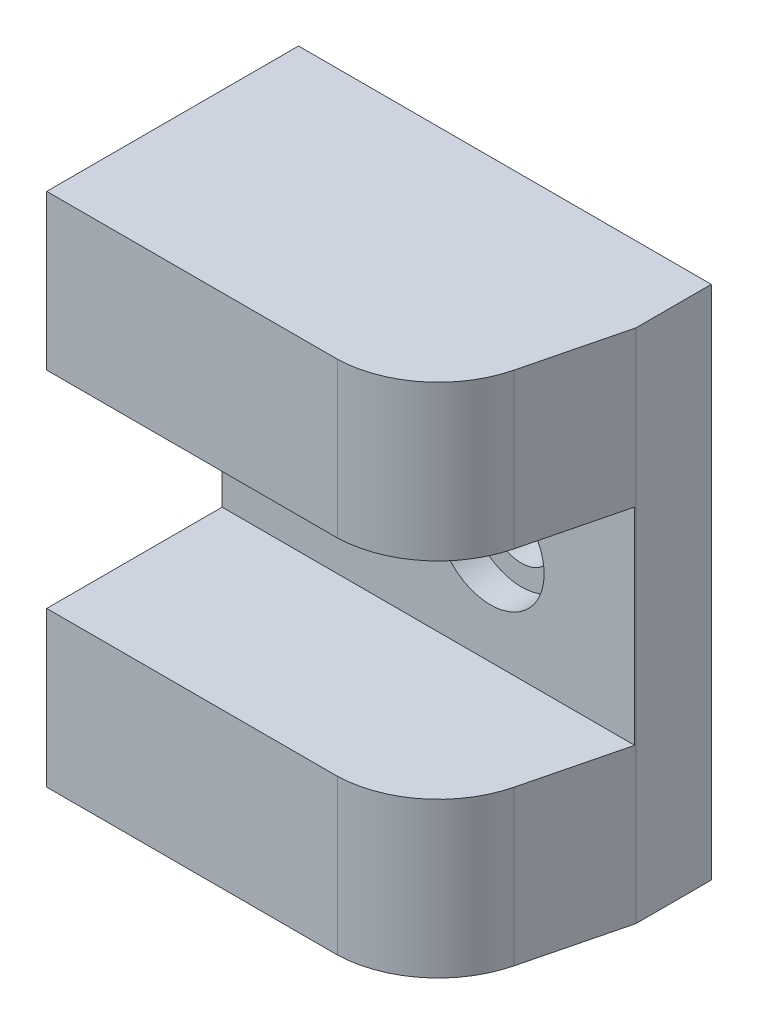
SolidWorks part; units mm, degrees
ref_plane "前视基准面" through (0, 0, 0) normal (0, 0, 1) x (1, 0, 0)
ref_plane "上视基准面" through (0, 0, 0) normal (0, 1, 0) x (1, 0, 0)
ref_plane "右视基准面" through (0, 0, 0) normal (1, 0, 0) x (0, 0, -1)
sketch "草图1" plane through (0, 0, 0) normal (0, 0, 1) x (1, 0, 0)
  line L0 (130, 105) -> (130, -105) construction
  line L1 (130, 80) -> (110, 80)
  line L2 (130, 80) -> (130, 105)
  line L4 (110, 80) -> (110, 105)
  line L5 (75, 105) -> (130, 105) construction
  line L6 (130, 105) -> (110, 105)
  dimension "D1" = 20
  dimension "D2" = 25
extrude "凸台-拉伸1" add sketch "草图1" along normal blind 12.2
sketch "草图2" plane through (0, 105, 0) normal (0, 1, 0) x (1, 0, 0)
  line L0 (130, -12.2) -> (130, 0) construction
  line L6 (128.82, -8.3843) -> (130, -3.6517)
  line L7 (128.9829, -8.558) -> (143.1288, 48.1782) construction
  line L8 (130, -3.6517) -> (130, -12.2)
  line L9 (128.9829, -8.558) -> (143.1288, 48.1782) construction
  line L10 (130, -12.2) -> (124.083, -12.2)
  line L11 (130, -12.2) -> (110, -12.2) construction
  arc A0 (123.9373, -12.5) -> (128.9829, -8.558) centre (123.9373, -7.3) ccw construction
  arc A1 (124.083, -12.2) -> (128.82, -8.3843) centre (123.9333, -7.1659) ccw
  arc A2 (123.9373, -12.5) -> (128.9829, -8.558) centre (123.9373, -7.3) ccw construction
  point P0 (123.9373, -7.1659)
  dimension "D1" = 5.917
  dimension "D2" = 0.4
extrude "切除-拉伸1" cut sketch "草图2" against normal blind 26.5
sketch "草图3" plane through (0, 0, 12.2) normal (0, 0, 1) x (1, 0, 0)
  line L0 (110, 92.5) -> (130, 92.5) construction
  line L1 (110, 105) -> (110, 80) construction
  line L4 (110, 97.5) -> (130, 97.5)
  line L5 (110, 97.5) -> (110, 87.5)
  line L6 (110, 87.5) -> (130, 87.5)
  line L7 (130, 97.5) -> (130, 87.5)
  line L8 (110, 97.5) -> (130, 87.5) construction
  line L9 (110, 87.5) -> (130, 97.5) construction
  point P6 (120, 92.5)
  dimension "D1" = 10
  dimension "D2" = 20
extrude "切除-拉伸2" cut sketch "草图3" against normal blind 8.5
sketch "草图4" plane through (0, 0, 3.7) normal (0, 0, 1) x (1, 0, 0)
  line L0 (110, 92.5) -> (129.988, 92.5) construction
  line L1 (110, 97.5) -> (110, 87.5) construction
  line L2 (129.988, 87.5) -> (129.988, 97.5) construction
  circle A0 centre (115, 92.5) radius 1.5
  circle A2 centre (123, 92.5) radius 1.5
  point P4 (0, 0)
  point P5 (129.988, 92.5)
  dimension "D1" = 3
  dimension "D2" = 8
  dimension "D3" = 5
hole_wizard "M3 六角头螺栓的柱形沉头孔1" positions "草图7" profile "草图8" counterbore size "M3" standard "GB" end condition through all
sketch "草图7" plane through (0, 0, 3.7) normal (0, 0, 1) x (1, 0, 0)
  point P0 (115, 92.5)
  point P3 (123, 92.5)
sketch "草图8" plane through (115, 92.5, 3.7) normal (1, 0, 0) x (0, -1, 0)
  line L0 (0, 0) -> (0, 3.7)
  line L1 (0, 3.7) -> (1.6, 3.7)
  line L3 (1.6, 3.7) -> (1.6, 1.5)
  line L4 (1.6, 1.5) -> (2.6, 1.5)
  line L5 (2.6, 1.5) -> (2.6, 0)
  line L7 (2.6, 0) -> (0, 0)
  line L11 (0, -6.35) -> (0, 107.95) construction
  dimension "通孔孔直径" = 3.2
  dimension "通孔孔深度" = 3.7
  dimension "柱形沉头孔直径" = 5.2
  dimension "柱形沉头孔深度" = 1.5
move or copy body "实体-移动/复制1" [suppressed] bodies to move or copy 109
